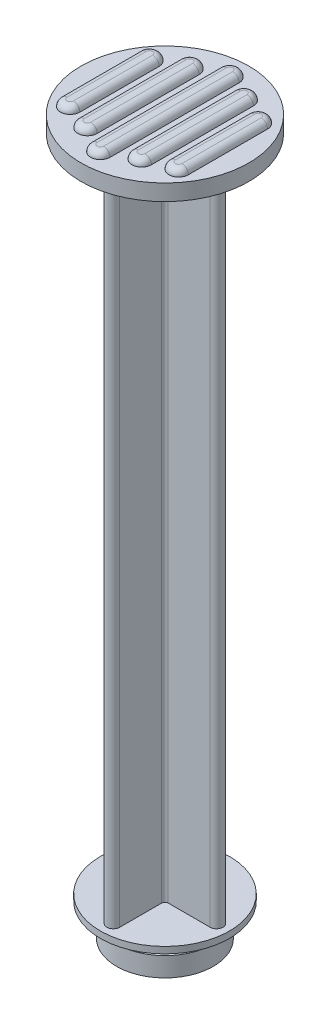
SolidWorks part; units mm, degrees
ref_plane "Front Plane" through (0, 0, 0) normal (0, 0, 1) x (1, 0, 0)
ref_plane "Top Plane" through (0, 0, 0) normal (0, 1, 0) x (1, 0, 0)
ref_plane "Right Plane" through (0, 0, 0) normal (1, 0, 0) x (0, 0, -1)
sketch "Sketch1" plane through (0, 0, 0) normal (0, 0, 1) x (1, 0, 0)
  line L0 (0, 0) -> (7.5, 0)
  line L1 (7.5, 0) -> (7.5, 3)
  line L2 (7.5, 3) -> (6, 3)
  line L3 (6, 3) -> (6, 5)
  line L4 (6, 5) -> (10, 5)
  line L5 (10, 5) -> (10, 6)
  line L6 (10, 6) -> (0, 6)
  line L7 (0, 6) -> (0, 0)
  point P3 (0, 0)
  point P10 (0, 0)
  dimension "D1" = 7.5
  dimension "D2" = 3
  dimension "D3" = 2
  dimension "D4" = 1
  dimension "D5" = 6
  dimension "D6" = 10
revolve "Revolve1" add sketch "Sketch1" angle 360 about L7
sketch "Sketch4" plane through (0, 6, 0) normal (0, 1, 0) x (1, 0, 0)
  line L1 (-7, 0) -> (-1, 0) construction
  line L2 (-1, 8) -> (-1, 1.5)
  line L3 (-8, -1) -> (-1.5, -1)
  line L4 (1, 8) -> (1, 1.5)
  line L5 (-8, 1) -> (-1.5, 1)
  line L9 (-10, 1) -> (10, 1) construction
  line L10 (-10, 0) -> (10, 0) construction
  line L11 (-10, -1) -> (10, -1) construction
  line L12 (1.5, 1) -> (8, 1)
  line L14 (1.5, -1) -> (8, -1)
  line L16 (-1, -1.5) -> (-1, -8)
  line L17 (1, -1.5) -> (1, -8)
  arc A1 (1, 8) -> (-1, 8) centre (0, 8) ccw
  arc A2 (-8, 1) -> (-8, -1) centre (-8, 0) ccw
  arc A3 (1, -8) -> (-1, -8) centre (0, -8) cw
  arc A4 (8, 1) -> (8, -1) centre (8, 0) cw
  arc A5 (-1.5, -1) -> (-1, -1.5) centre (-1.5, -1.5) cw
  arc A6 (1.5, -1) -> (1, -1.5) centre (1.5, -1.5) ccw
  arc A7 (1.5, 1) -> (1, 1.5) centre (1.5, 1.5) cw
  arc A8 (-1.5, 1) -> (-1, 1.5) centre (-1.5, 1.5) ccw
  point P3 (-1, -1)
  point P12 (1, -1)
  dimension "D3" = 8
  dimension "D5" = 0.5
  dimension "D4" = 8
  dimension "D1" = 1
  dimension "D2" = 1
extrude "Boss-Extrude1" add sketch "Sketch4" along normal blind 102 contours A3 L16 A5 L3 A2 L5 A8 L2 A1 L4 A7 L12 A4 L14 A6 L17
sketch "Sketch5" plane through (0, 108, 0) normal (0, 1, 0) x (1, 0, 0)
  circle A0 centre (0, 0) radius 13
  dimension "D1" = 26
extrude "Boss-Extrude2" add sketch "Sketch5" along normal blind 2.5
sketch "Sketch6" plane through (0, 110.5, 0) normal (0, 1, 0) x (1, 0, 0)
  line L0 (0, 11.5) -> (0, -11.5) construction
  line L1 (-4.2, 8) -> (-4.2, -7.7993) construction
  line L2 (-8.4, 6) -> (-8.4, -6.2751) construction
  line L3 (-13, 0) -> (13, 0) construction
  line L4 (-1.5, 10) -> (-1.5, -10)
  line L5 (1.5, 10) -> (1.5, -10)
  line L6 (-5.7, 8) -> (-5.7, -7.7993)
  line L7 (-9.9, 6) -> (-9.9, -6.2751)
  line L8 (-2.7, 8) -> (-2.7, -7.7993)
  line L9 (-6.9, 6) -> (-6.9, -6.2751)
  line L10 (-1.5, 13) -> (-1.5, -13) construction
  line L11 (0, 13) -> (0, -13) construction
  line L12 (1.5, 13) -> (1.5, -13) construction
  line L13 (-9.9, 6) -> (-9.9, -6.2751) construction
  line L14 (-5.7, 8) -> (-5.7, -7.7993) construction
  line L15 (-2.7, 8) -> (-2.7, -7.7993) construction
  line L16 (9.9, 6) -> (9.9, -6.2751)
  line L17 (6.9, 6) -> (6.9, -6.2751)
  line L18 (5.7, 8) -> (5.7, -7.7993)
  line L19 (2.7, 8) -> (2.7, -7.7993)
  circle A0 centre (0, 0) radius 13 construction
  arc A1 (1.5, 10) -> (-1.5, 10) centre (0, 10) ccw
  arc A2 (-2.7, 8) -> (-5.7, 8) centre (-4.2, 8) ccw
  arc A3 (-6.9, 6) -> (-9.9, 6) centre (-8.4, 6) ccw
  arc A4 (-9.9, -6.2751) -> (-6.9, -6.2751) centre (-8.4, -6.2751) ccw
  arc A5 (-5.7, -7.7993) -> (-2.7, -7.7993) centre (-4.2, -7.7993) ccw
  arc A6 (1.5, -10) -> (-1.5, -10) centre (0, -10) cw
  arc A7 (6.9, 6) -> (9.9, 6) centre (8.4, 6) cw
  arc A8 (9.9, -6.2751) -> (6.9, -6.2751) centre (8.4, -6.2751) cw
  arc A9 (2.7, 8) -> (5.7, 8) centre (4.2, 8) cw
  arc A10 (5.7, -7.7993) -> (2.7, -7.7993) centre (4.2, -7.7993) cw
  point P26 (0, 0)
  point P33 (-9.8827, 5.7731)
  point P38 (-5.6959, 7.8885)
  point P40 (-2.7, 8)
  point P42 (-2.7, 8)
  point P43 (-2.7, 8)
  dimension "D3" = 4.2
  dimension "D4" = 4.2
  dimension "D7" = 10
  dimension "D8" = 8
  dimension "D9" = 6
extrude "Boss-Extrude3" add sketch "Sketch6" along normal blind 1
fillet "Fillet1" radius 1 20 edges at (9.9, 111.5, 0.1375) (8.4, 111.5, 7.7751) (6.9, 111.5, 0.1375) (8.4, 111.5, -7.5) (5.7, 111.5, -0.1004) (4.2, 111.5, 9.2993) (2.7, 111.5, -0.1004) (4.2, 111.5, -9.5) (1.5, 111.5, 0) (0, 111.5, 11.5) (-1.5, 111.5, 0) (0, 111.5, -11.5) (-2.7, 111.5, -0.1004) (-4.2, 111.5, 9.2993) (-5.7, 111.5, -0.1004) (-4.2, 111.5, -9.5) (-6.9, 111.5, 0.1375) (-8.4, 111.5, 7.7751) (-9.9, 111.5, 0.1375) (-8.4, 111.5, -7.5)
